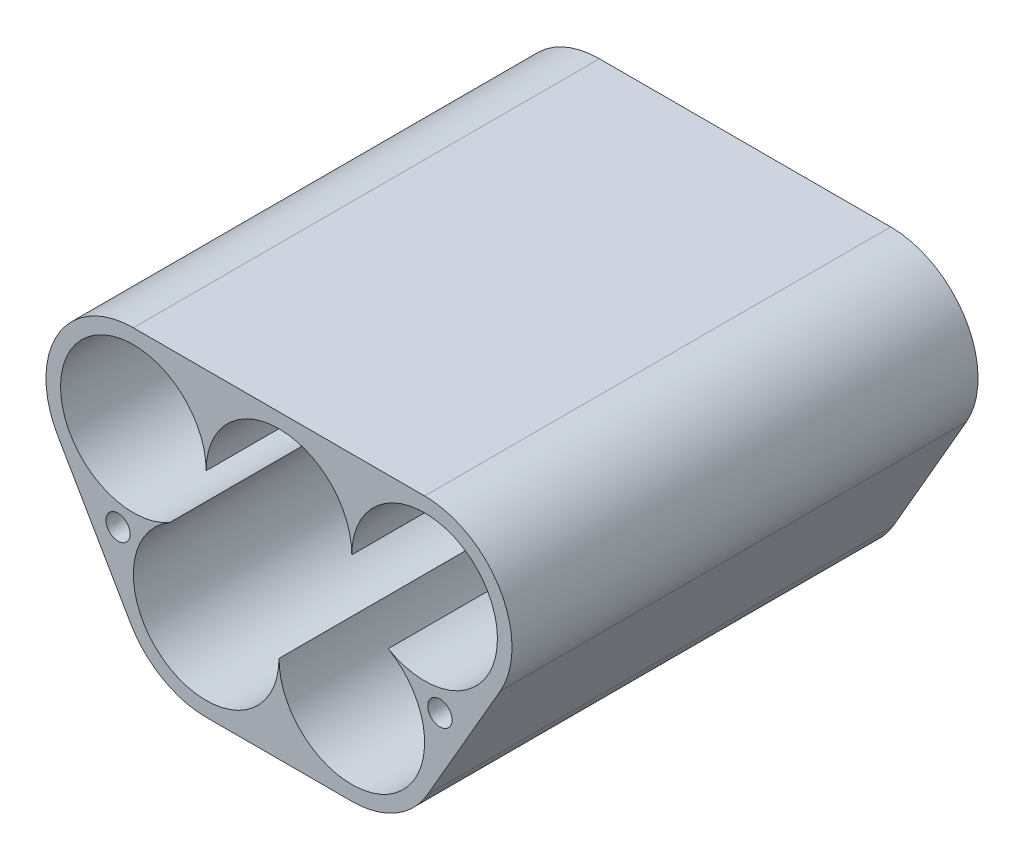
SolidWorks part; units mm, degrees
ref_plane "Front Plane" through (0, 0, 0) normal (0, 0, 1) x (1, 0, 0)
ref_plane "Top Plane" through (0, 0, 0) normal (0, 1, 0) x (1, 0, 0)
ref_plane "Right Plane" through (0, 0, 0) normal (1, 0, 0) x (0, 0, -1)
sketch "Sketch1" plane through (0, 0, 0) normal (0, 0, 1) x (1, 0, 0)
  line L4 (7.5, -21.9904) -> (22.5, -21.9904)
  line L5 (30.2942, -17.4904) -> (37.7942, -4.5)
  line L6 (30, 9) -> (0, 9)
  line L7 (-7.7942, -4.5) -> (-0.2942, -17.4904)
  line L8 (7.5, -21.9904) -> (22.5, -21.9904)
  line L9 (30.2942, -17.4904) -> (37.7942, -4.5)
  line L10 (30, 9) -> (0, 9)
  line L11 (-7.7942, -4.5) -> (-0.2942, -17.4904)
  arc A4 (22.5, -21.9904) -> (30.2942, -17.4904) centre (22.5, -12.9904) ccw
  arc A5 (37.7942, -4.5) -> (30, 9) centre (30, 0) ccw
  arc A6 (0, 9) -> (-7.7942, -4.5) centre (0, 0) ccw
  arc A7 (-0.2942, -17.4904) -> (7.5, -21.9904) centre (7.5, -12.9904) ccw
  arc A8 (22.5, -21.9904) -> (30.2942, -17.4904) centre (22.5, -12.9904) ccw
  arc A9 (37.7942, -4.5) -> (30, 9) centre (30, 0) ccw
  arc A10 (0, 9) -> (-7.7942, -4.5) centre (0, 0) ccw
  arc A11 (-0.2942, -17.4904) -> (7.5, -21.9904) centre (7.5, -12.9904) ccw
  circle A99 centre (7.5, -12.9904) radius 7.5 construction
  circle A100 centre (22.5, -12.9904) radius 7.5 construction
  circle A101 centre (30, 0) radius 7.5 construction
  circle A102 centre (15, 0) radius 7.5 construction
  circle A103 centre (0, 0) radius 7.5 construction
  arc A104 (3.75, -6.4952) -> (15, -12.9904) centre (7.5, -12.9904) ccw
  arc A105 (15, -12.9904) -> (26.25, -6.4952) centre (22.5, -12.9904) ccw
  arc A106 (26.25, -6.4952) -> (22.5, 0) centre (30, 0) ccw
  arc A107 (22.5, 0) -> (7.5, 0) centre (15, 0) ccw
  arc A108 (7.5, 0) -> (3.75, -6.4952) centre (0, 0) ccw
  dimension "D1" = 0
extrude "Boss-Extrude1" add sketch "Sketch1" along normal blind 48
sketch "Sketch2" plane through (0, 0, 0) normal (0, 0, -1) x (-1, 0, 0)
  circle A0 centre (1.5761, -9.5702) radius 2.75 construction
  circle A1 centre (-31.575, -9.5702) radius 2.75 construction
  circle A2 centre (1.5761, -9.5702) radius 2.75 construction
  circle A3 centre (-31.575, -9.5702) radius 2.75 construction
  circle A4 centre (1.5761, -9.5702) radius 1.25
  circle A5 centre (-31.575, -9.5702) radius 1.25
  dimension "D1" = 2.5
extrude "Cut-Extrude1" cut sketch "Sketch2" against normal through all
ref_plane "Plane1" through (0, 0, 24) normal (0, 0, 1) x (1, 0, 0)
sketch "Sketch3" plane through (0, -21.9904, 0) normal (0, -1, 0) x (1, 0, 0)
  line L0 (15, 48) -> (15, 0) construction
  line L1 (7.5, 48) -> (22.5, 48) construction
  line L2 (7.5, 0) -> (22.5, 0) construction
ref_plane "Plane2" through (15, 0, 0) normal (-1, 0, 0) x (0, 0, -1)
